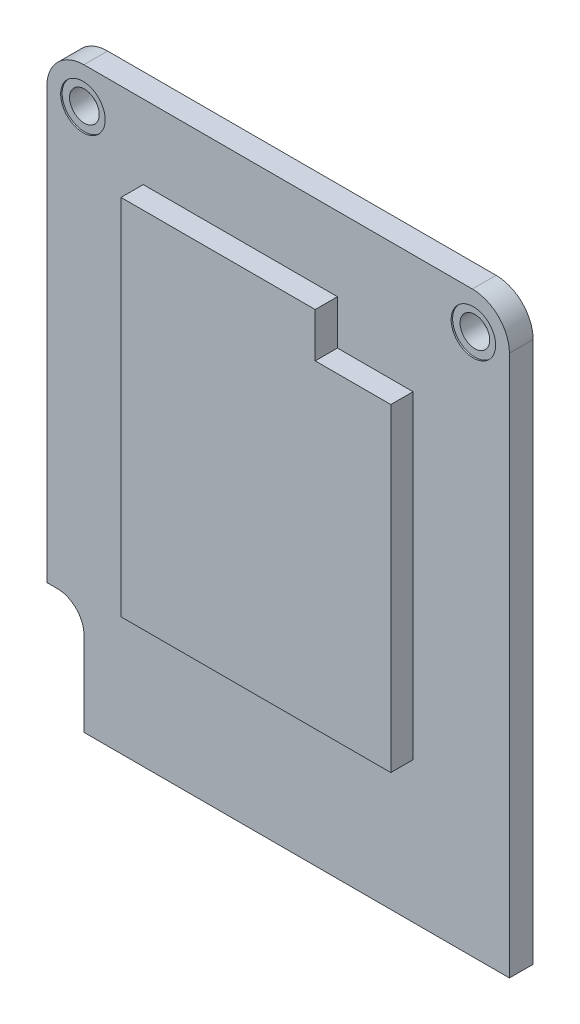
SolidWorks part; units mm, degrees
ref_plane "Front" through (0, 0, 0) normal (0, 0, 1) x (1, 0, 0)
ref_plane "Top" through (0, 0, 0) normal (0, 1, 0) x (1, 0, 0)
ref_plane "Right" through (0, 0, 0) normal (1, 0, 0) x (0, 0, -1)
sketch "Sketch1" plane through (0, 0, 0) normal (0, 0, 1) x (1, 0, 0)
  line L0 (-15.6, -12) -> (-14.9, -12)
  line L1 (-15.6, -19.5) -> (15.6, -19.5)
  line L2 (-15.6, -19.5) -> (-15.6, 17)
  line L3 (-13.1, 19.5) -> (13.1, 19.5)
  line L4 (15.6, -19.5) -> (15.6, 17)
  line L5 (-15.6, -19.5) -> (15.6, 19.5) construction
  line L6 (-15.6, 19.5) -> (15.6, -19.5) construction
  line L7 (-13.1, -13.8) -> (-13.1, -19.5)
  line L8 (-13.17, 19.5) -> (-13.17, -49980.5) construction
  line L9 (13.17, 19.5) -> (13.17, -49980.5) construction
  line L10 (-13.1, 17) -> (49986.9, 17) construction
  arc A0 (15.6, 17) -> (13.1, 19.5) centre (13.1, 17) ccw
  arc A1 (-13.1, 19.5) -> (-15.6, 17) centre (-13.1, 17) ccw
  arc A2 (-13.1, -13.8) -> (-14.9, -12) centre (-14.9, -13.8) ccw
  circle A3 centre (13.17, 17) radius 1
  circle A4 centre (-13.17, 17) radius 1
  circle A5 centre (-13.17, 17) radius 1.5
  circle A6 centre (13.17, 17) radius 1.5
  point P0 (0, 0)
  point P17 (-13.1, -12)
  dimension "D3" = 2.5
  dimension "D6" = 1.8
  dimension "D9" = 2
  dimension "D1" = 31.2
  dimension "D2" = 39
  dimension "D4" = 2.5
  dimension "D5" = 7.5
  dimension "D7" = 2.43
  dimension "D8" = 2.43
  dimension "D10" = 2.5
  dimension "D11" = 0.5
extrude "Boss-Extrude1" add sketch "Sketch1" along normal blind 1.6 contours A2 L7 L1 L4 A0 L3 A1 L2 L0 A6 A5 region at (0.2197, -0.0038, 0)
extrude "Boss-Extrude2" add sketch "Sketch1<5>" along normal offset from surface (1.4 mm away) 0.1 from offset 0.1 contours A6 A3 | A5 A4 region at (-14.6276, 17, 0) region at (11.7124, 17, 0) up to face at (14.67, 17, 1.6)
sketch "Sketch1<5>" plane through (0, 0, 0) normal (0, 0, 1) x (1, 0, 0) same geometry as "Sketch1"
sketch "Sketch2" plane through (0, 0, 1.6) normal (0, 0, 1) x (1, 0, 0)
  line L0 (0, 0) -> (0, 50000) construction
  line L1 (-13.1, 19.5) -> (13.1, 19.5) construction
  line L2 (-9.1, 14.5) -> (4, 14.5)
  line L3 (4, 14.5) -> (4, 11.5)
  line L4 (4, 11.5) -> (9.1, 11.5)
  line L5 (9.1, 11.5) -> (9.1, -10)
  line L6 (9.1, -10) -> (-9.1, -10)
  line L7 (-9.1, -10) -> (-9.1, 14.5)
  line L8 (-15.6, -12) -> (-15.6, 17) construction
  line L9 (15.6, -19.5) -> (15.6, 17) construction
  point P5 (0, 19.5)
  dimension "D1" = 6.5
  dimension "D2" = 6.5
  dimension "D3" = 5
  dimension "D4" = 2
  dimension "D5" = 4
  dimension "D6" = 3
extrude "Boss-Extrude3" add sketch "Sketch2" along normal blind 1.5
